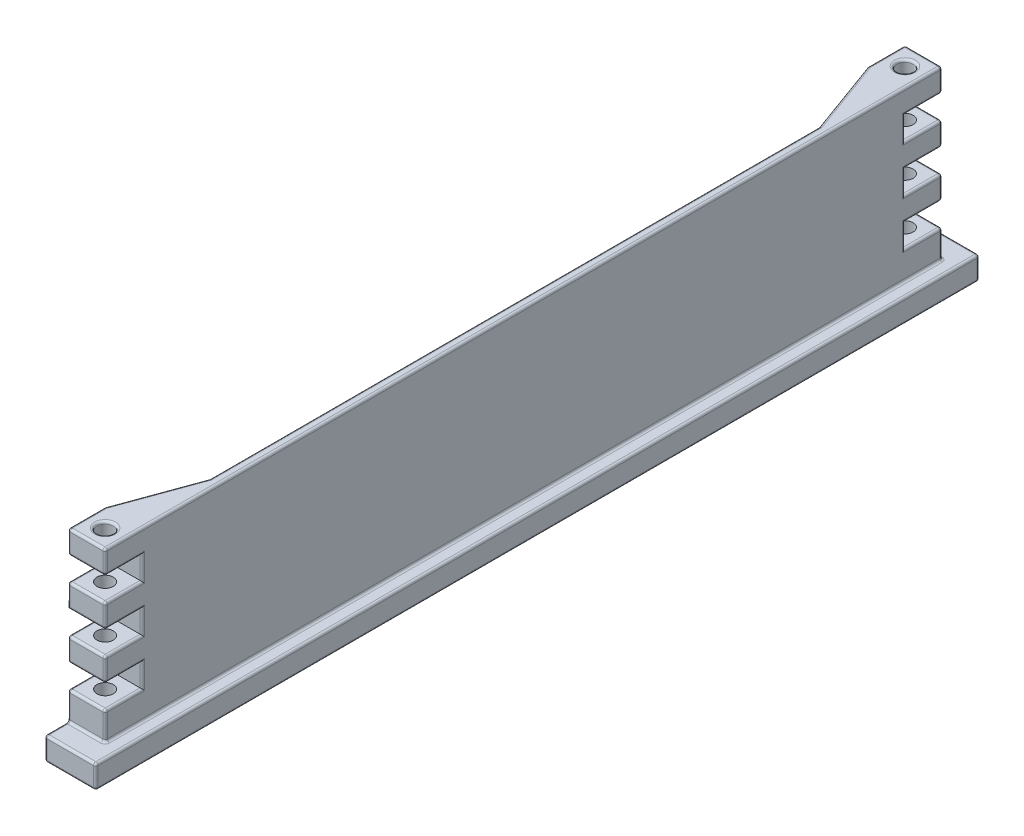
SolidWorks part; units mm, degrees
ref_plane "Front Plane" through (0, 0, 0) normal (0, 0, 1) x (1, 0, 0)
ref_plane "Top Plane" through (0, 0, 0) normal (0, 1, 0) x (1, 0, 0)
ref_plane "Right Plane" through (0, 0, 0) normal (1, 0, 0) x (0, 0, -1)
sketch "Sketch1" plane through (0, 0, 0) normal (1, 0, 0) x (0, 0, -1)
  line L1 (-45, -20.5) -> (45, -20.5)
  line L2 (-45, -4.5) -> (-45, 0.5)
  line L3 (-37, 20.5) -> (45, 20.5)
  line L4 (45, -20.5) -> (45, 20.5)
  line L5 (-45, -20.5) -> (45, 20.5) construction
  line L6 (-45, 20.5) -> (45, -20.5) construction
  line L7 (-50, -15.5) -> (-50, -20.5)
  line L8 (-50, -20.5) -> (-45, -20.5)
  line L12 (-37, 20.5) -> (-37, 15.5) construction
  line L13 (-37, 15.5) -> (-45, 15.5)
  line L14 (-37, 15.5) -> (-37, 10.5)
  line L15 (-37, 10.5) -> (-45, 10.5)
  line L16 (-37, 10.5) -> (-37, 5.5) construction
  line L17 (-37, 5.5) -> (-37, 0.5)
  line L18 (-37, 0.5) -> (-37, -4.5) construction
  line L19 (-37, -4.5) -> (-37, -9.5)
  line L20 (-37, 20.5) -> (-45, 20.5)
  line L21 (-45, 15.5) -> (-45, 20.5)
  line L22 (-37, -9.5) -> (-45, -9.5)
  line L23 (-37, -4.5) -> (-45, -4.5)
  line L24 (-37, 0.5) -> (-45, 0.5)
  line L25 (-37, 5.5) -> (-45, 5.5)
  line L26 (-45, 5.5) -> (-45, 10.5)
  line L42 (-50, -15.5) -> (-45, -15.5)
  line L43 (-45, -15.5) -> (-45, -9.5)
  point P0 (0, 0)
  dimension "D1" = 41
  dimension "D2" = 90
  dimension "D3" = 5
  dimension "D4" = 8
  dimension "D5" = 5
  dimension "D6" = 5
extrude "Boss-Extrude1" add sketch "Sketch1" along normal blind 8 contours L19 L22 L2 L7 L8 L1 L4 L3 L12 L14 L16 L17 L18 | L18 L24 L2 L23 | L25 L16 L15 L2 | L13 L12 L3 L2 region at (0, -0.2253, -1.0382)
sketch "Sketch3" plane through (8, 0, 0) normal (1, 0, 0) x (0, 0, -1)
  line L3 (45, -20.5) -> (-50, -20.5)
  line L5 (-50, -15.5) -> (-50, -20.5)
  line L6 (-50, -15.5) -> (45, -15.5)
  line L7 (45, -20.5) -> (45, 20.5) construction
  line L8 (45, -15.5) -> (45, -20.5)
sketch "Sketch7" plane through (0, -20.5, 0) normal (0, -1, 0) x (1, 0, 0)
  line L0 (0, 45) -> (8, 45)
  line L1 (0, 50) -> (0, -45) construction
  line L2 (4, 37) -> (4, 37.738) construction
  line L3 (8, 45) -> (8, 37)
  line L4 (8, 37) -> (0, 37)
  line L5 (0, 37) -> (0, 45)
  line L6 (8, 50) -> (0, 50) construction
  line L8 (8, 37) -> (0, 45) construction
  line L10 (1.175, 39.369) -> (4, 37.738)
  line L11 (4, 37.738) -> (6.825, 39.369)
  line L12 (6.825, 39.369) -> (6.825, 42.631)
  line L13 (6.825, 42.631) -> (4, 44.262)
  line L14 (4, 44.262) -> (1.175, 42.631)
  line L15 (1.175, 42.631) -> (1.175, 39.369)
  circle A0 centre (4, 41) radius 1.75
  circle A1 centre (4, 41) radius 2.825 construction
  dimension "D4" = 5.65
  dimension "D5" = 3.5
  dimension "D1" = 5
  dimension "D2" = 8
  dimension "D3" = 8
extrude "Cut-Extrude3" cut sketch "Sketch7" against normal through all both and the other way through all contours A0 region at (4, -20.5, 41)
extrude "Boss-Extrude2" add sketch "Sketch3" along normal blind 3
extrude "Cut-Extrude4" cut sketch "Sketch7<3>" against normal blind 8 and the other way through all contours L14 L15 L10 L11 L12 L13 A0 region at (1.2613, -20.5, 41)
sketch "Sketch7<3>" plane through (0, -20.5, 0) normal (0, -1, 0) x (1, 0, 0) same geometry as "Sketch7"
sketch "Sketch8" plane through (0, 20.5, 0) normal (0, 1, 0) x (1, 0, 0)
  line L0 (0, -37) -> (6, -20.5151)
  line L1 (0, -45) -> (0, 45) construction
  line L2 (6, -20.5151) -> (6, 45)
  line L3 (8, 45) -> (0, 45) construction
  line L4 (0, -37) -> (0, 45)
  line L5 (0, 45) -> (6, 45)
  dimension "D1" = 2
  dimension "D2" = 8
  dimension "D3" = 200
extrude "Cut-Extrude5" cut sketch "Sketch8" against normal blind 39
mirror "Mirror2" about plane through (8, 0, -45) normal (0, 0, 1) of bodies 111 109
fillet "Fillet1" radius 0.5 87 edges at (4, -9.5, 45) (4, -15.5, 45) (0, -12.5, 45) (5.5, -15.5, 50) (5.5, -20.5, 50) (0, -18, 50) (5.5, -20.5, -140) (5.5, -15.5, -140) (0, -18, -140) (4, -15.5, -135) (4, -9.5, -135) (0, -12.5, -135) (4, -4.5, -135) (4, 0.5, -135) (0, -2, -135) (4, 5.5, -135) (4, 10.5, -135) (0, 8, -135) (4, 15.5, -135) (0, 18, -135) (4, 15.5, 45) (0, 18, 45) (4, 10.5, 45) (4, 5.5, 45) (0, 8, 45) (4, 0.5, 45) (4, -4.5, 45) (0, -2, 45) (6, 1, 20.5151) (6, 1, -110.5151) (8, -9.5, 41) (8, -7, 37) (8, -4.5, 41) (8, -2, 45) (8, 0.5, 41) (8, 3, 37) (8, 5.5, 41) (8, 8, 45) (8, 10.5, 41) (8, 13, 37) (8, 15.5, 41) (8, 18, 45) (8, 18, -135) (8, 15.5, -131) (8, 13, -127) (8, 10.5, -131) (8, 8, -135) (8, 5.5, -131) (8, 3, -127) (8, 0.5, -131) (8, -2, -135) (8, -4.5, -131) (8, -7, -127) (8, -9.5, -131) (8, -12.5, -135) (8, -15.5, -45) (8, -12.5, 45) (4, 20.5, -129.25) (4, 20.5, 39.25) (6, 20.5, -45) (3, 20.5, -118.7576) (0, 20.5, -131) (4, 20.5, -135) (8, 20.5, -45) (4, 20.5, 45) (0, 20.5, 41) (3, 20.5, 28.7576) (0, -4.5, 41) (0, 0.5, 41) (0, 10.5, 41) (0, 15.5, 41) (0, -9.5, 41) (0, -15.5, 47.5) (0, 15.5, -131) (0, 10.5, -131) (0, 5.5, -131) (0, -4.5, -131) (0, 0.5, -131) (0, -9.5, -131) (0, -15.5, -137.5) (0, -20.5, -45) (6, -18.5, -45) (0, -18.5, -45) (11, -18, 50) (11, -18, -140) (11, -20.5, -45) (11, -15.5, -45)
